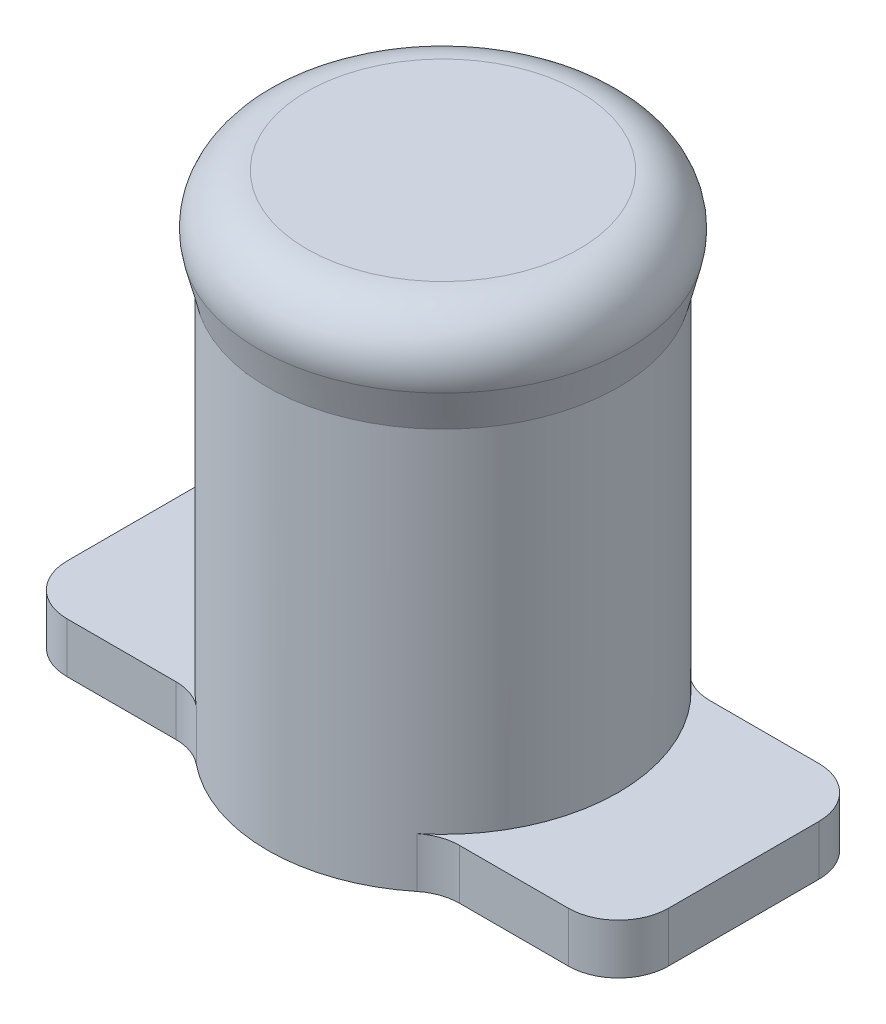
SolidWorks part; units mm, degrees
ref_plane "Front Plane" through (0, 0, 0) normal (0, 0, 1) x (1, 0, 0)
ref_plane "Top Plane" through (0, 0, 0) normal (0, 1, 0) x (1, 0, 0)
ref_plane "Right Plane" through (0, 0, 0) normal (1, 0, 0) x (0, 0, -1)
sketch "Sketch1" plane through (0, 0, 0) normal (0, 0, 1) x (1, 0, 0)
  line L0 (0, 0) -> (0, 10)
  line L1 (0, 10) -> (4, 10)
  line L5 (3.5, 0) -> (0, 0)
  line L8 (3.5, 0) -> (3.5, 8)
  line L9 (3.5, 8) -> (4, 10)
  dimension "D1" = 4
  dimension "D2" = 10
  dimension "D3" = 3.5
  dimension "D4" = 8
revolve "Revolve1" add sketch "Sketch1" angle 360 about L0
sketch "Sketch3" plane through (0, 0, 0) normal (0, -1, 0) x (1, 0, 0)
  line L1 (-1.8, -1.8) -> (1.8, -1.8)
  line L2 (-1.8, -1.8) -> (-1.8, 1.8)
  line L3 (-1.8, 1.8) -> (1.8, 1.8)
  line L4 (1.8, -1.8) -> (1.8, 1.8)
  line L5 (-1.8, -1.8) -> (1.8, 1.8) construction
  line L6 (-1.8, 1.8) -> (1.8, -1.8) construction
  point P0 (0, 0)
  dimension "D2" = 3.6
extrude "Cut-Extrude2" cut sketch "Sketch3" against normal blind 3.5
sketch "Sketch4" plane through (0, 0, 0) normal (0, 1, 0) x (1, 0, 0)
  line L0 (-3.9, 0) -> (0, 0) construction
  line L1 (-1.8, 2.5) -> (-6, 2.5)
  line L2 (-1.8, 2.5) -> (-1.8, -2.5)
  line L3 (-1.8, -2.5) -> (-6, -2.5)
  line L4 (-6, 2.5) -> (-6, -2.5)
  line L5 (-1.8, 2.5) -> (-6, -2.5) construction
  line L6 (-1.8, -2.5) -> (-6, 2.5) construction
  line L7 (6, -2.5) -> (1.8, -2.5)
  line L8 (6, -2.5) -> (6, 2.5)
  line L9 (6, 2.5) -> (1.8, 2.5)
  line L10 (1.8, -2.5) -> (1.8, 2.5)
  line L11 (6, -2.5) -> (1.8, 2.5) construction
  line L12 (6, 2.5) -> (1.8, -2.5) construction
  line L13 (0, 0) -> (3.9, 0) construction
  line L14 (-1.8, -1.8) -> (-1.8, 1.8) construction
  line L15 (-3.5, 3.4123) -> (-3.5, -3.7854) construction
  circle A0 centre (0, 0) radius 3.5 construction
  point P0 (-3.9, 0)
  point P6 (3.9, 0)
  dimension "D1" = 5
  dimension "D2" = 2.5
extrude "Boss-Extrude1" add sketch "Sketch4" along normal blind 1
fillet "Fillet1" radius 1 9 edges at (2.4495, 0.5, 2.5) (6, 0.5, 2.5) (6, 0.5, -2.5) (2.4495, 0.5, -2.5) (-2.4495, 0.5, -2.5) (-6, 0.5, -2.5) (-6, 0.5, 2.5) (-2.4495, 0.5, 2.5) (0, 10, -4)
